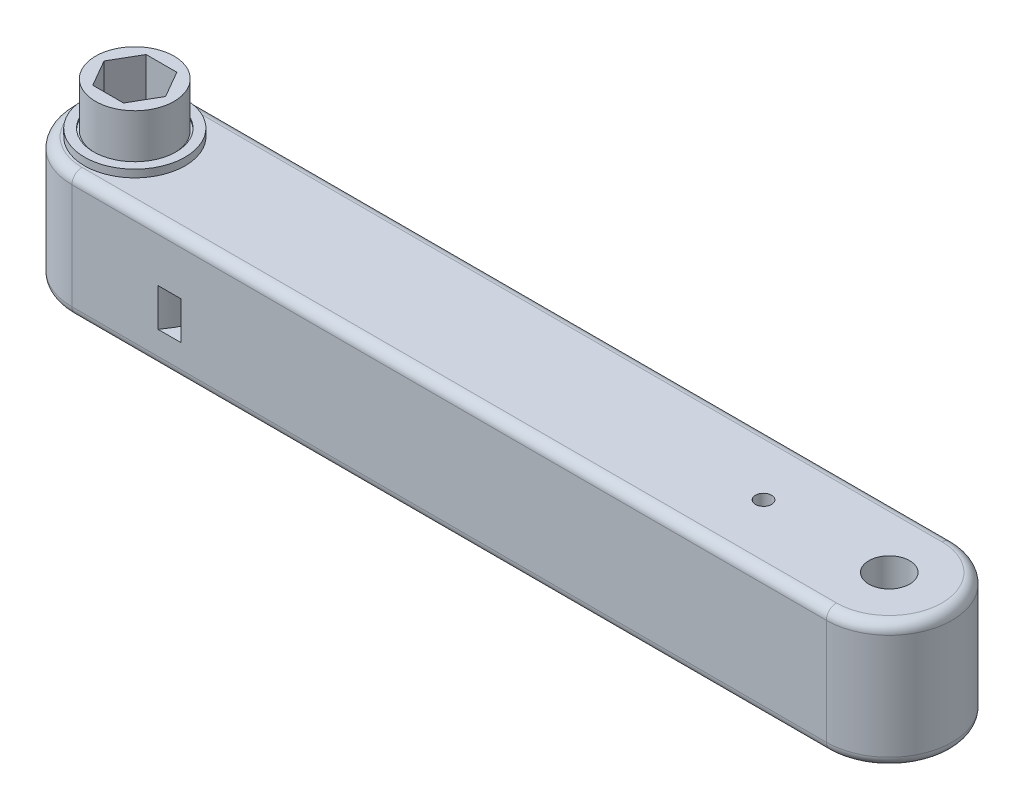
SolidWorks part; units mm, degrees
ref_plane "Alzado" through (0, 0, 0) normal (0, 0, 1) x (1, 0, 0)
ref_plane "Planta" through (0, 0, 0) normal (0, 1, 0) x (1, 0, 0)
ref_plane "Vista lateral" through (0, 0, 0) normal (1, 0, 0) x (0, 0, -1)
sketch "Croquis2" plane through (0, 0, 0) normal (0, 1, 0) x (1, 0, 0)
  line L0 (0, 0) -> (150, 0) construction
  line L1 (0, -12.5) -> (150, -12.5)
  line L2 (0, 12.5) -> (150, 12.5)
  arc A0 (150, -12.5) -> (150, 12.5) centre (150, 0) ccw
  arc A1 (0, 12.5) -> (0, -12.5) centre (0, 0) ccw
  dimension "D1" = 150
  dimension "D2" = 25
extrude "Saliente-Extruir1" add sketch "Croquis2" along normal blind 25
sketch "Croquis5" plane through (0, 25, 0) normal (0, 1, 0) x (1, 0, 0)
  circle A0 centre (150, 0) radius 4.05
  circle A1 centre (125, 0) radius 1.6
  dimension "D2" = 3.2
  dimension "D3" = 8.1
  dimension "D1" = 25
extrude "Cortar-Extruir1" cut sketch "Croquis5" against normal blind 51.5
sketch "Croquis9" plane through (0, 0, 0) normal (0, 0, 1) x (1, 0, 0)
  line L0 (0, 25) -> (0, 35) construction
  line L1 (0, 25) -> (0, 35)
  line L2 (0, 25) -> (150, 25) construction
  line L3 (0, 35) -> (7.8, 35)
  line L4 (7.8, 35) -> (7.8, 26.5)
  line L5 (8.2, 26.5) -> (10, 26.5)
  line L6 (10, 26.5) -> (10, 25)
  line L7 (10, 25) -> (0, 25)
  line L10 (7.8, 26.5) -> (7.8, 26.1)
  line L11 (7.8, 26.1) -> (8.2, 26.1)
  line L12 (8.2, 26.5) -> (8.2, 26.1)
  dimension "D1" = 10
  dimension "D2" = 7.8
  dimension "D4" = 1.5
  dimension "D5" = 10
  dimension "D6" = 0.4
  dimension "D7" = 0.4
revolve "Revolución2" add sketch "Croquis9" angle 360 about L0
sketch "Croquis1" plane through (0, 0, 0) normal (0, 0, 1) x (1, 0, 0)
  line L0 (0, 20) -> (0, 0) construction
  line L1 (9.3, 17) -> (1, 20)
  line L2 (9.3, 17) -> (9.3, 12.7)
  line L3 (9.3, 12.7) -> (7.3, 12.7)
  line L4 (7.3, 12.7) -> (7.3, 8.6547)
  line L6 (9.3, 7.5) -> (9.3, 0)
  line L7 (9.3, 0) -> (1, 0)
  line L8 (1, 20) -> (1, 0)
  line L9 (13.75, 0) -> (-13.75, 0) construction
  line L10 (0, -13.75) -> (0, 13.75) construction
  line L11 (9.3, 7.5) -> (7.3, 8.6547)
  dimension "D1" = 6.3
  dimension "D2" = 4.3
  dimension "D3" = 1
  dimension "D4" = 17
  dimension "D5" = 7.5
  dimension "D6" = 20
  dimension "D7" = 8.3
  dimension "D8" = 30
revolve "Cortar-Revolución1" cut sketch "Croquis1" angle 360 about L8
fillet "Redondeo2" radius 2 8 edges at (-12.5, 0, 0) (75, 0, -12.5) (162.5, 0, 0) (-12.5, 25, 0) (75, 25, -12.5) (162.5, 25, 0) (75, 0, 12.5) (75, 25, 12.5)
sketch "Croquis10" plane through (0, 35, 0) normal (0, 1, 0) x (1, 0, 0)
  line L1 (6.1199, 0) -> (3.06, 5.3)
  line L2 (3.06, 5.3) -> (-3.06, 5.3)
  line L3 (-3.06, 5.3) -> (-6.1199, 0)
  line L4 (-6.1199, 0) -> (-3.06, -5.3)
  line L5 (-3.06, -5.3) -> (3.06, -5.3)
  line L6 (3.06, -5.3) -> (6.1199, 0)
  circle A0 centre (0, 0) radius 5.3 construction
  dimension "D1" = 10.6
extrude "Cortar-Extruir2" cut sketch "Croquis10" against normal up to next
sketch "Croquis12" plane through (0, 0, 0) normal (1, 0, 0) x (0, 0, -1)
  line L0 (8.3, 7.5) -> (6.3, 8.6547)
  line L1 (-8.3, 7.5) -> (-6.3, 8.6547)
  line L2 (8.3, 17) -> (8.3, 12.7)
  line L3 (6.3, 12.7) -> (8.3, 12.7)
  line L4 (6.3, 12.7) -> (6.3, 8.6547)
  line L6 (8.3, 7.5) -> (8.3, 0)
  line L8 (13.75, 0) -> (-13.75, 0) construction
  line L9 (8.3, 0) -> (-8.3, 0)
  line L11 (8.3, 17) -> (0, 20)
  line L12 (-8.3, 17) -> (-8.3, 12.7)
  line L13 (-8.3, 12.7) -> (-6.3, 12.7)
  line L14 (-6.3, 12.7) -> (-6.3, 8.6547)
  line L16 (-8.3, 7.5) -> (-8.3, 0)
  line L17 (-10.5, 0) -> (10.5, 0) construction
  line L18 (0, 19.25) -> (0, -19.25) construction
  line L19 (0, 20) -> (-8.3, 17)
  dimension "D1" = 4.3
  dimension "D2" = 7.5
  dimension "D3" = 2
  dimension "D4" = 2
  dimension "D5" = 17
  dimension "D6" = 20
  dimension "D7" = 8.3
  dimension "D8" = 30
  dimension "D9" = 30
  dimension "D10" = 8.3
extrude "Cortar-Extruir4" cut sketch "Croquis12" against normal through all and the other way blind 1
sketch "Croquis13" plane through (0, 0, 0) normal (0, 0, 1) x (1, 0, 0)
  line L0 (0, 0) -> (0, 35) construction
  line L1 (21.2204, 14.1989) -> (25.0523, 14.1989)
  line L2 (21.2204, 14.1989) -> (21.2204, 6.6629)
  line L3 (21.2204, 6.6629) -> (25.0523, 6.6629)
  line L4 (25.0523, 14.1989) -> (25.0523, 6.6629)
  line L5 (3.06, 35) -> (-3.06, 35) construction
revolve "Cortar-Revolución2" cut sketch "Croquis13" angle 360 about L0
